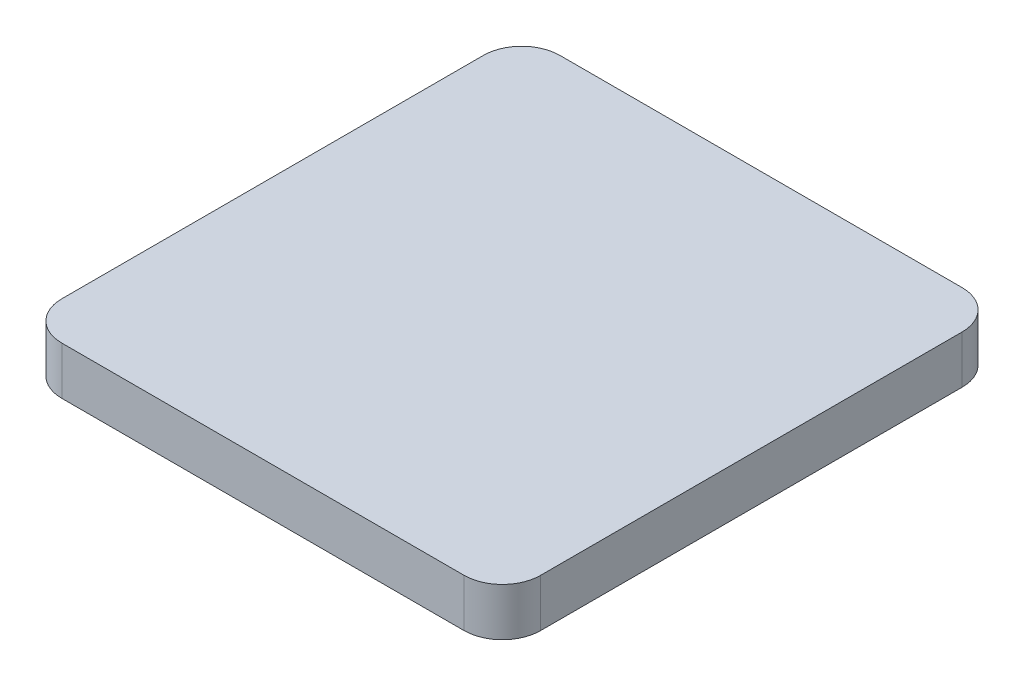
SolidWorks part; units mm, degrees
material "Acrylic (Medium-high impact)"
ref_plane "Front Plane" through (0, 0, 0) normal (0, 0, 1) x (1, 0, 0)
ref_plane "Top Plane" through (0, 0, 0) normal (0, 1, 0) x (1, 0, 0)
ref_plane "Right Plane" through (0, 0, 0) normal (1, 0, 0) x (0, 0, -1)
ref_plane "Plane1" through (0, 0, 0) normal (0, 1, 0) x (1, 0, 0)
sketch "Sketch1" plane through (0, 0, 0) normal (0, 1, 0) x (1, 0, 0)
  line L1 (0, 0) -> (31.75, 0)
  line L2 (0, 0) -> (0, 33.03)
  line L3 (0, 33.03) -> (31.75, 33.03)
  line L4 (31.75, 0) -> (31.75, 33.03)
  dimension "D1" = 33.03
  dimension "D2" = 31.75
extrude "Boss-Extrude1" add sketch "Sketch1" along normal blind 3.175
ref_plane "Plane2" through (0, 3.175, 0) normal (0, 1, 0) x (1, 0, 0)
fillet "Fillet1" radius 2.54 4 edges at (0, 1.5875, -33.03) (31.75, 1.5875, -33.03) (31.75, 1.5875, 0) (0, 1.5875, 0)
